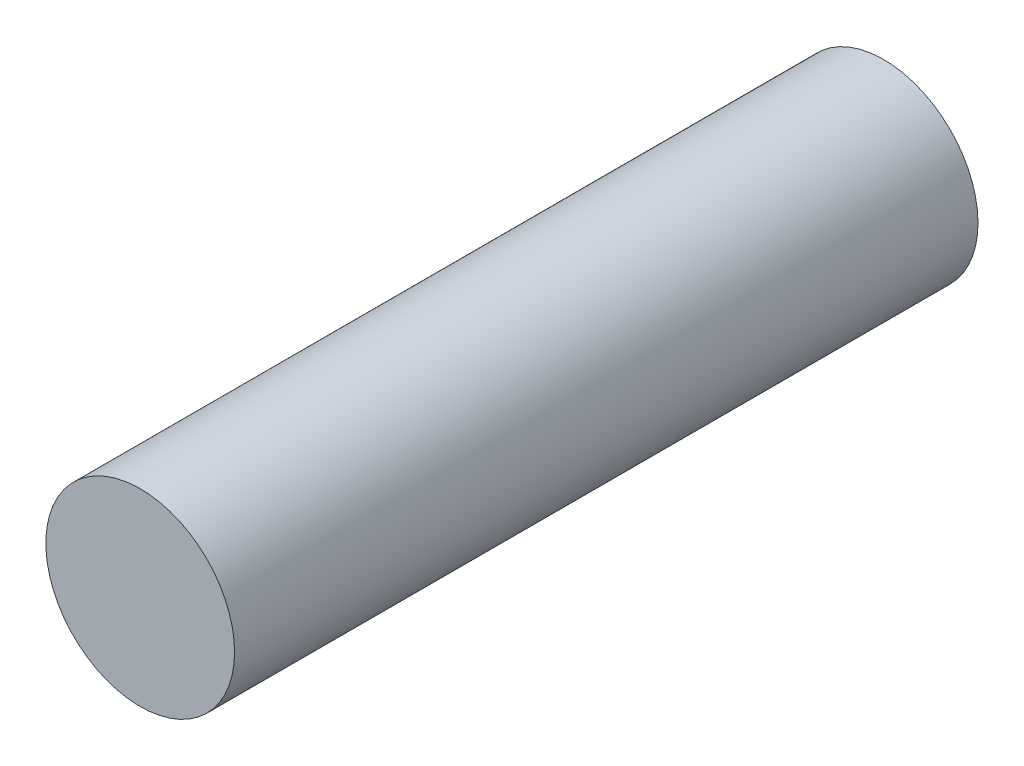
SolidWorks part; units mm, degrees
material "6061-T6 (SS)"
ref_plane "Front Plane" through (0, 0, 0) normal (0, 0, 1) x (1, 0, 0)
ref_plane "Top Plane" through (0, 0, 0) normal (0, 1, 0) x (1, 0, 0)
ref_plane "Right Plane" through (0, 0, 0) normal (1, 0, 0) x (0, 0, -1)
sketch "Sketch1" plane through (0, 0, 0) normal (0, 0, 1) x (1, 0, 0)
  circle A0 centre (0, 0) radius 35.5406
  dimension "D1" = 71.0812
extrude "Boss-Extrude1" add sketch "Sketch1" along normal mid plane 280
sketch "Sketch2" plane through (0, 0, -140) normal (0, 0, -1) x (-1, 0, 0)
  line L0 (-35.5406, 0) -> (35.5406, 0) construction
  circle A0 centre (0, 0) radius 35.5406 construction
  point P7 (0, 0)
ref_axis "mating" through (102.9859, 0, -140) along (-1, 0, 0)
